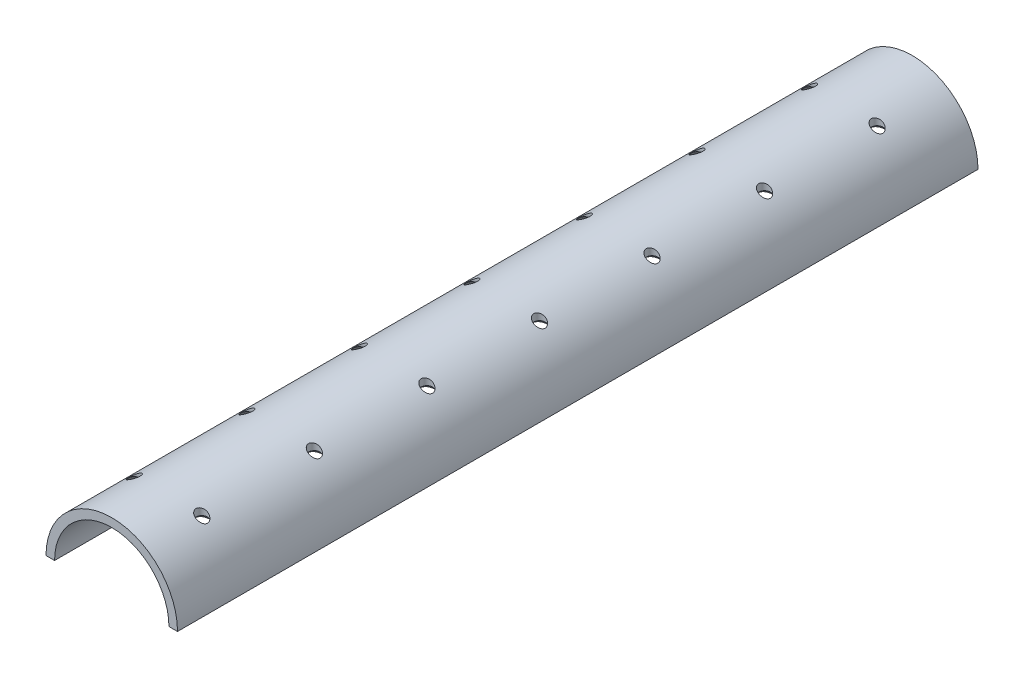
SolidWorks part; units mm, degrees
ref_plane "Front Plane" through (0, 0, 0) normal (0, 0, 1) x (1, 0, 0)
ref_plane "Top Plane" through (0, 0, 0) normal (0, 1, 0) x (1, 0, 0)
ref_plane "Right Plane" through (0, 0, 0) normal (1, 0, 0) x (0, 0, -1)
sketch "Sketch2" plane through (0, 0, 0) normal (0, 0, 1) x (1, 0, 0)
  circle A0 centre (0, 0) radius 29.21
  dimension "D1" = 58.42
extrude "Boss-Extrude1" add sketch "Sketch2" against normal blind 355.6
sketch "Sketch3" plane through (0, 0, 0) normal (0, 0, 1) x (1, 0, 0)
  circle A0 centre (0, 0) radius 25.4
  dimension "D1" = 50.8
extrude "Cut-Extrude1" cut sketch "Sketch3" against normal through all
sketch "Sketch4" plane through (0, 0, 0) normal (0, 1, 0) x (1, 0, 0)
  line L1 (-29.21, 355.6) -> (29.21, 355.6)
  line L2 (-29.21, 355.6) -> (-29.21, 0)
  line L3 (-29.21, 0) -> (29.21, 0)
  line L4 (29.21, 355.6) -> (29.21, 0)
extrude "Cut-Extrude2" cut sketch "Sketch4" against normal up to next
sketch "Sketch5" plane through (0, 0, 0) normal (0, 1, 0) x (1, 0, 0)
  line L0 (0, 319.7815) -> (0, 0) construction
  line L1 (-29.21, 0) -> (29.21, 0) construction
  point P3 (15, 25)
  point P6 (-15, 25)
  point P7 (15, 75)
  point P9 (-15, 75)
  point P10 (15, 125)
  point P11 (-15, 125)
  point P12 (15, 175)
  point P13 (-15, 175)
  point P14 (15, 225)
  point P15 (-15, 225)
  point P16 (15, 275)
  point P17 (-15, 275)
  point P18 (15, 325)
  point P19 (-15, 325)
  dimension "D1" = 25
  dimension "D2" = 15
  dimension "D4" = 50
  dimension "D3" = 7
hole_wizard "CSK for #10 Flat Head Machine Screw1" positions "Sketch9" profile "Sketch10" countersink size "#10" standard "ANSI Inch" end condition through all
sketch "Sketch9" plane through (0, 0, 0) normal (0, -1, 0) x (-1, 0, 0)
  point P0 (-15, 25)
  point P3 (-15, 75)
  point P6 (15, 25)
  point P9 (15, 75)
  point P13 (-15, 125)
  point P16 (15, 125)
  point P19 (15, 175)
  point P22 (-15, 175)
  point P25 (-15, 225)
  point P28 (15, 225)
  point P31 (15, 275)
  point P34 (-15, 275)
  point P37 (-15, 325)
  point P40 (15, 325)
sketch "Sketch10" plane through (15, 0, -25) normal (1, 0, 0) x (0, 0, -1)
  line L0 (0, 0) -> (0, 29.21)
  line L1 (0, 29.21) -> (2.5527, 29.21)
  line L2 (2.5527, 29.21) -> (2.5527, 23.1882)
  line L3 (2.5527, 23.1882) -> (4.8895, 20.5)
  line L4 (4.8895, 20.5) -> (4.8895, 0)
  line L6 (4.8895, 0) -> (0, 0)
  line L7 (-2.5527, 23.1882) -> (-4.8895, 20.5) construction
  line L11 (0, -6.35) -> (0, 107.95) construction
  dimension "Thru Hole Dia." = 5.1054
  dimension "Thru Hole Depth" = 29.21
  dimension "C'Sink Dia." = 9.779
  dimension "C'Sink Angle" = 82
  dimension "Head Clearance" = 20.5
